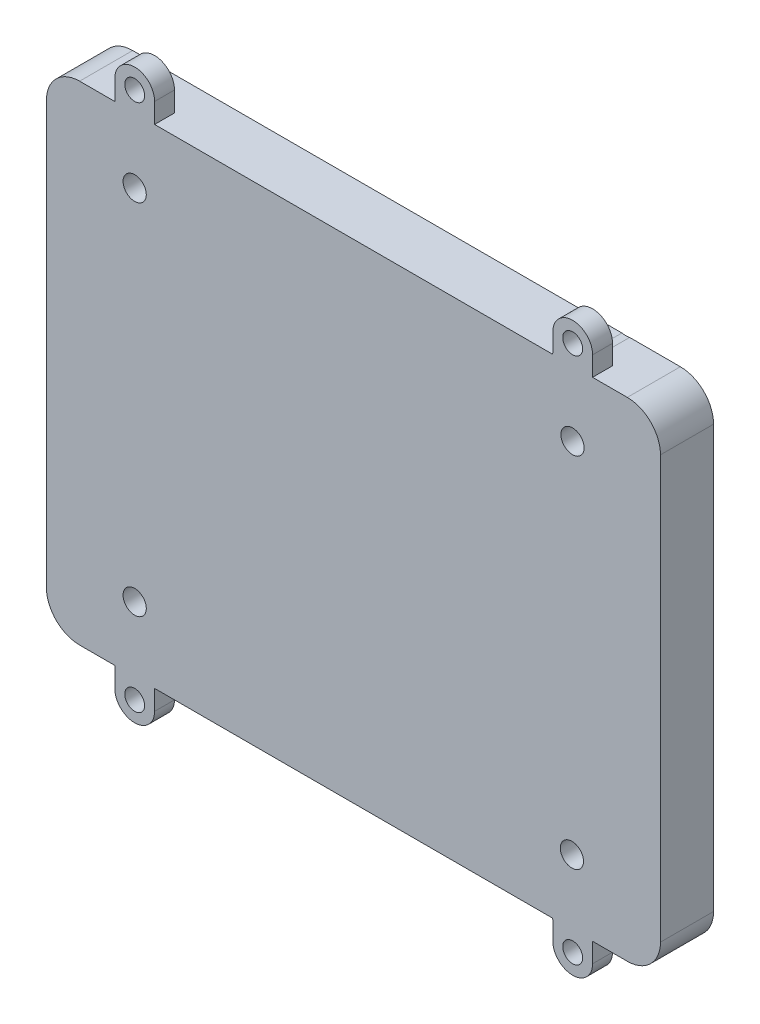
SolidWorks part; units mm, degrees
ref_plane "前视基准面" through (0, 0, 0) normal (0, 0, 1) x (1, 0, 0)
ref_plane "上视基准面" through (0, 0, 0) normal (0, 1, 0) x (1, 0, 0)
ref_plane "右视基准面" through (0, 0, 0) normal (1, 0, 0) x (0, 0, -1)
sketch "draft" plane through (0, 0, 0) normal (0, 0, 1) x (1, 0, 0)
  line L1 (-39.27, 34.8) -> (39.33, 34.8)
  line L2 (-44.27, 29.8) -> (-44.27, -29.8)
  line L3 (-39.27, -34.8) -> (39.33, -34.8)
  line L4 (44.33, 29.8) -> (44.33, -29.8)
  line L5 (-44.27, 29.8) -> (-39.27, 34.8)
  line L6 (-44.27, -29.8) -> (-39.27, -34.8)
  line L7 (39.33, -34.8) -> (44.33, -29.8)
  line L8 (39.33, 34.8) -> (44.33, 29.8)
  line L146 (-41.27, -36.8) -> (41.27, -36.8)
  line L147 (-46.27, -31.8) -> (-46.27, 31.8)
  line L148 (-41.27, 36.8) -> (41.27, 36.8)
  line L149 (46.27, -31.8) -> (46.27, 31.8)
  line L151 (-46.27, 36.8) -> (46.27, -36.8) construction
  line L152 (-32.97, 39.8) -> (-32.97, 27) construction
  line L153 (-35.97, 39.8) -> (-35.97, 36.8)
  line L154 (-29.97, 39.8) -> (-29.97, 36.8)
  line L155 (30.0392, 39.7478) -> (30.034, 36.7478)
  line L156 (36.0392, 39.7374) -> (36.0339, 36.7374)
  line L157 (36.0392, -39.7374) -> (36.0339, -36.7374)
  line L158 (30.0392, -39.7478) -> (30.034, -36.7478)
  line L159 (-29.97, -39.8) -> (-29.97, -36.8)
  line L160 (-35.97, -39.8) -> (-35.97, -36.8)
  arc A0 (41.27, 36.8) -> (46.27, 31.8) centre (41.27, 31.8) cw
  arc A1 (46.27, -31.8) -> (41.27, -36.8) centre (41.27, -31.8) cw
  arc A2 (-41.27, -36.8) -> (-46.27, -31.8) centre (-41.27, -31.8) cw
  arc A3 (-46.27, 31.8) -> (-41.27, 36.8) centre (-41.27, 31.8) cw
  circle A4 centre (-32.97, 27) radius 1.75
  circle A5 centre (-32.97, -27) radius 1.75
  circle A6 centre (32.923, -27.0573) radius 1.75
  circle A7 centre (33.0169, 26.9426) radius 1.75
  circle A8 centre (-32.97, 39.8) radius 1.5
  circle A9 centre (-32.97, 39.8) radius 3
  circle A10 centre (33.0392, 39.7426) radius 3
  circle A11 centre (33.0392, 39.7426) radius 1.5
  circle A12 centre (33.0392, -39.7426) radius 1.5
  circle A13 centre (33.0392, -39.7426) radius 3
  circle A14 centre (-32.97, -39.8) radius 3
  circle A15 centre (-32.97, -39.8) radius 1.5
  point P0 (0, 0)
  point P1 (-44.27, 34.8)
  point P2 (44.33, -34.8)
  point P3 (-44.27, -34.8)
  point P4 (44.33, 34.8)
  point P21 (0, 0)
  line B0 (-43.97, 29.5) -> (-38.97, 34.5)
  line B1 (-38.97, 34.5) -> (39.03, 34.5)
  line B2 (-43.97, 29.5) -> (-43.97, -29.5)
  line B3 (-38.97, -34.5) -> (39.03, -34.5)
  line B4 (44.03, 29.5) -> (44.03, -29.5)
  line B5 (-43.97, -29.5) -> (-38.97, -34.5)
  line B6 (39.03, -34.5) -> (44.03, -29.5)
  line B7 (39.03, 34.5) -> (44.03, 29.5)
  line B8 (0.03, 34.5) -> (-0.03, -34.5) construction
  line B9 (44.03, 0) -> (-43.97, 0) construction
  line B10 (-36.73, -31.1) -> (-33.73, -31.1)
  line B11 (-36.73, 34.5) -> (-33.73, 34.5)
  line B12 (-36.73, 34.5) -> (-36.73, 31.1)
  line B13 (-36.73, 31.1) -> (-33.73, 31.1)
  line B14 (-33.73, 34.5) -> (-33.73, 31.1)
  line B15 (-33.73, -34.5) -> (-33.73, -31.1)
  line B16 (-36.73, -34.5) -> (-33.73, -34.5)
  line B17 (-36.73, -34.5) -> (-36.73, -31.1)
  line B18 (-32.33, 34.5) -> (-32.33, 31.1)
  line B19 (-32.33, 34.5) -> (-29.33, 34.5)
  line B20 (-29.33, 34.5) -> (-29.33, 31.1)
  line B21 (-32.33, 31.1) -> (-29.33, 31.1)
  line B22 (-32.33, -31.1) -> (-29.33, -31.1)
  line B23 (-29.33, -34.5) -> (-29.33, -31.1)
  line B24 (-32.33, -34.5) -> (-29.33, -34.5)
  line B25 (-32.33, -34.5) -> (-32.33, -31.1)
  line B26 (-27.93, 34.5) -> (-27.93, 31.1)
  line B27 (-27.93, 34.5) -> (-24.93, 34.5)
  line B28 (-24.93, 34.5) -> (-24.93, 31.1)
  line B29 (-27.93, 31.1) -> (-24.93, 31.1)
  line B30 (-27.93, -31.1) -> (-24.93, -31.1)
  line B31 (-24.93, -34.5) -> (-24.93, -31.1)
  line B32 (-27.93, -34.5) -> (-24.93, -34.5)
  line B33 (-27.93, -34.5) -> (-27.93, -31.1)
  line B34 (-23.53, 34.5) -> (-23.53, 31.1)
  line B35 (-23.53, 34.5) -> (-20.53, 34.5)
  line B36 (-20.53, 34.5) -> (-20.53, 31.1)
  line B37 (-23.53, 31.1) -> (-20.53, 31.1)
  line B38 (-23.53, -31.1) -> (-20.53, -31.1)
  line B39 (-20.53, -34.5) -> (-20.53, -31.1)
  line B40 (-23.53, -34.5) -> (-20.53, -34.5)
  line B41 (-23.53, -34.5) -> (-23.53, -31.1)
  line B42 (-19.13, 34.5) -> (-19.13, 31.1)
  line B43 (-19.13, 34.5) -> (-16.13, 34.5)
  line B44 (-16.13, 34.5) -> (-16.13, 31.1)
  line B45 (-19.13, 31.1) -> (-16.13, 31.1)
  line B46 (-19.13, -31.1) -> (-16.13, -31.1)
  line B47 (-16.13, -34.5) -> (-16.13, -31.1)
  line B48 (-19.13, -34.5) -> (-16.13, -34.5)
  line B49 (-19.13, -34.5) -> (-19.13, -31.1)
  line B50 (-14.73, 34.5) -> (-14.73, 31.1)
  line B51 (-14.73, 34.5) -> (-11.73, 34.5)
  line B52 (-11.73, 34.5) -> (-11.73, 31.1)
  line B53 (-14.73, 31.1) -> (-11.73, 31.1)
  line B54 (-14.73, -31.1) -> (-11.73, -31.1)
  line B55 (-11.73, -34.5) -> (-11.73, -31.1)
  line B56 (-14.73, -34.5) -> (-11.73, -34.5)
  line B57 (-14.73, -34.5) -> (-14.73, -31.1)
  line B58 (-10.33, 34.5) -> (-10.33, 31.1)
  line B59 (-10.33, 34.5) -> (-7.33, 34.5)
  line B60 (-7.33, 34.5) -> (-7.33, 31.1)
  line B61 (-10.33, 31.1) -> (-7.33, 31.1)
  line B62 (-10.33, -31.1) -> (-7.33, -31.1)
  line B63 (-7.33, -34.5) -> (-7.33, -31.1)
  line B64 (-10.33, -34.5) -> (-7.33, -34.5)
  line B65 (-10.33, -34.5) -> (-10.33, -31.1)
  line B66 (-5.93, 34.5) -> (-5.93, 31.1)
  line B67 (-5.93, 34.5) -> (-2.93, 34.5)
  line B68 (-2.93, 34.5) -> (-2.93, 31.1)
  line B69 (-5.93, 31.1) -> (-2.93, 31.1)
  line B70 (-5.93, -31.1) -> (-2.93, -31.1)
  line B71 (-2.93, -34.5) -> (-2.93, -31.1)
  line B72 (-5.93, -34.5) -> (-2.93, -34.5)
  line B73 (-5.93, -34.5) -> (-5.93, -31.1)
  line B74 (-1.53, 34.5) -> (-1.53, 31.1)
  line B75 (-1.53, 34.5) -> (1.47, 34.5)
  line B76 (1.47, 34.5) -> (1.47, 31.1)
  line B77 (-1.53, 31.1) -> (1.47, 31.1)
  line B78 (-1.53, -31.1) -> (1.47, -31.1)
  line B79 (1.47, -34.5) -> (1.47, -31.1)
  line B80 (-1.53, -34.5) -> (1.47, -34.5)
  line B81 (-1.53, -34.5) -> (-1.53, -31.1)
  line B82 (2.87, 34.5) -> (2.87, 31.1)
  line B83 (2.87, 34.5) -> (5.87, 34.5)
  line B84 (5.87, 34.5) -> (5.87, 31.1)
  line B85 (2.87, 31.1) -> (5.87, 31.1)
  line B86 (2.87, -31.1) -> (5.87, -31.1)
  line B87 (5.87, -34.5) -> (5.87, -31.1)
  line B88 (2.87, -34.5) -> (5.87, -34.5)
  line B89 (2.87, -34.5) -> (2.87, -31.1)
  line B90 (7.27, 34.5) -> (7.27, 31.1)
  line B91 (7.27, 34.5) -> (10.27, 34.5)
  line B92 (10.27, 34.5) -> (10.27, 31.1)
  line B93 (7.27, 31.1) -> (10.27, 31.1)
  line B94 (7.27, -31.1) -> (10.27, -31.1)
  line B95 (10.27, -34.5) -> (10.27, -31.1)
  line B96 (7.27, -34.5) -> (10.27, -34.5)
  line B97 (7.27, -34.5) -> (7.27, -31.1)
  line B98 (11.67, 34.5) -> (11.67, 31.1)
  line B99 (11.67, 34.5) -> (14.67, 34.5)
  line B100 (14.67, 34.5) -> (14.67, 31.1)
  line B101 (11.67, 31.1) -> (14.67, 31.1)
  line B102 (11.67, -31.1) -> (14.67, -31.1)
  line B103 (14.67, -34.5) -> (14.67, -31.1)
  line B104 (11.67, -34.5) -> (14.67, -34.5)
  line B105 (11.67, -34.5) -> (11.67, -31.1)
  line B106 (16.07, 34.5) -> (16.07, 31.1)
  line B107 (16.07, 34.5) -> (19.07, 34.5)
  line B108 (19.07, 34.5) -> (19.07, 31.1)
  line B109 (16.07, 31.1) -> (19.07, 31.1)
  line B110 (16.07, -31.1) -> (19.07, -31.1)
  line B111 (19.07, -34.5) -> (19.07, -31.1)
  line B112 (16.07, -34.5) -> (19.07, -34.5)
  line B113 (16.07, -34.5) -> (16.07, -31.1)
  line B114 (20.47, 34.5) -> (20.47, 31.1)
  line B115 (20.47, 34.5) -> (23.47, 34.5)
  line B116 (23.47, 34.5) -> (23.47, 31.1)
  line B117 (20.47, 31.1) -> (23.47, 31.1)
  line B118 (20.47, -31.1) -> (23.47, -31.1)
  line B119 (23.47, -34.5) -> (23.47, -31.1)
  line B120 (20.47, -34.5) -> (23.47, -34.5)
  line B121 (20.47, -34.5) -> (20.47, -31.1)
  line B122 (24.87, 34.5) -> (24.87, 31.1)
  line B123 (24.87, 34.5) -> (27.87, 34.5)
  line B124 (27.87, 34.5) -> (27.87, 31.1)
  line B125 (24.87, 31.1) -> (27.87, 31.1)
  line B126 (24.87, -31.1) -> (27.87, -31.1)
  line B127 (27.87, -34.5) -> (27.87, -31.1)
  line B128 (24.87, -34.5) -> (27.87, -34.5)
  line B129 (24.87, -34.5) -> (24.87, -31.1)
  line B130 (29.27, 34.5) -> (29.27, 31.1)
  line B131 (29.27, 34.5) -> (32.27, 34.5)
  line B132 (32.27, 34.5) -> (32.27, 31.1)
  line B133 (29.27, 31.1) -> (32.27, 31.1)
  line B134 (29.27, -31.1) -> (32.27, -31.1)
  line B135 (32.27, -34.5) -> (32.27, -31.1)
  line B136 (29.27, -34.5) -> (32.27, -34.5)
  line B137 (29.27, -34.5) -> (29.27, -31.1)
  line B138 (33.67, 34.5) -> (33.67, 31.1)
  line B139 (33.67, 34.5) -> (36.67, 34.5)
  line B140 (36.67, 34.5) -> (36.67, 31.1)
  line B141 (33.67, 31.1) -> (36.67, 31.1)
  line B142 (33.67, -31.1) -> (36.67, -31.1)
  line B143 (36.67, -34.5) -> (36.67, -31.1)
  line B144 (33.67, -34.5) -> (36.67, -34.5)
  line B145 (33.67, -34.5) -> (33.67, -31.1)
  line B146 (-36.73, 34.5) -> (-32.33, 34.5) construction
  circle B147 centre (-32.97, 27) radius 1.25
  circle B148 centre (33.0169, 26.9426) radius 1.25
  circle B149 centre (33.0169, -26.9426) radius 1.25
  circle B150 centre (-32.97, -27) radius 1.25
  dimension "D15" = 5
  dimension "D18" = 3
  dimension "D10" = 2
  dimension "D14" = 2
  dimension "D17" = 3
sketch_block_instance "upper_face-1"
sketch_block "块1" parameters "D9"=2.5, "D10"=3, "D11"=4.4
extrude "凸台-拉伸1" add sketch "draft" along normal blind 3 contours A9 A8 | A9 L153 L148 | A9 L148 L154 | A10 L148 A11 | L148 A10 L155 | L156 A10 L148 | A13 L146 A12 | A13 L157 L146 | A13 L146 L158 | L160 A14 L146 | A14 A15 | L146 A14 L159 | L147 A3 L148 A0 L149 A1 L146 A2 | A9 | A8 region at (-35.2999, -37.4701, 0) region at (-30.6401, -37.4701, 0) region at (-30.9087, -37.7387, 0) region at (30.653, -37.468, 0) region at (-35.2999, 37.4701, 0) region at (33.0392, -36.8844, 0) region at (-30.6401, 37.4701, 0) region at (-35.0313, 37.7387, 0) region at (35.4201, -37.4654, 0) region at (30.653, 37.468, 0) region at (30.7842, 37.8945, 0) region at (35.4201, 37.4654, 0)
extrude "凸台-拉伸2" add sketch "draft<5>" against normal blind 5 contours A3 L147 A2 L146 A1 L149 A0 L148 L1 L8 L4 L7 L3 region at (-43.9695, -34.4995, 0)
sketch "draft<5>" plane through (0, 0, 0) normal (0, 0, 1) x (1, 0, 0) same geometry as "draft"
extrude "切除-拉伸7" cut sketch "draft<6>" along normal through all contours A6 | A7 | A4 | A5 | B147 | B148 | B150 | B149 region at (-34.6705, 27, 0) region at (-34.6705, -27, 0) region at (31.2225, -27.0573, 0) region at (31.3164, 26.9426, 0) region at (-32.97, 27, 0) region at (33.0169, 26.9426, 0) region at (-32.97, -27, 0)
sketch "draft<6>" plane through (0, 0, 0) normal (0, 0, 1) x (1, 0, 0) same geometry as "draft"
